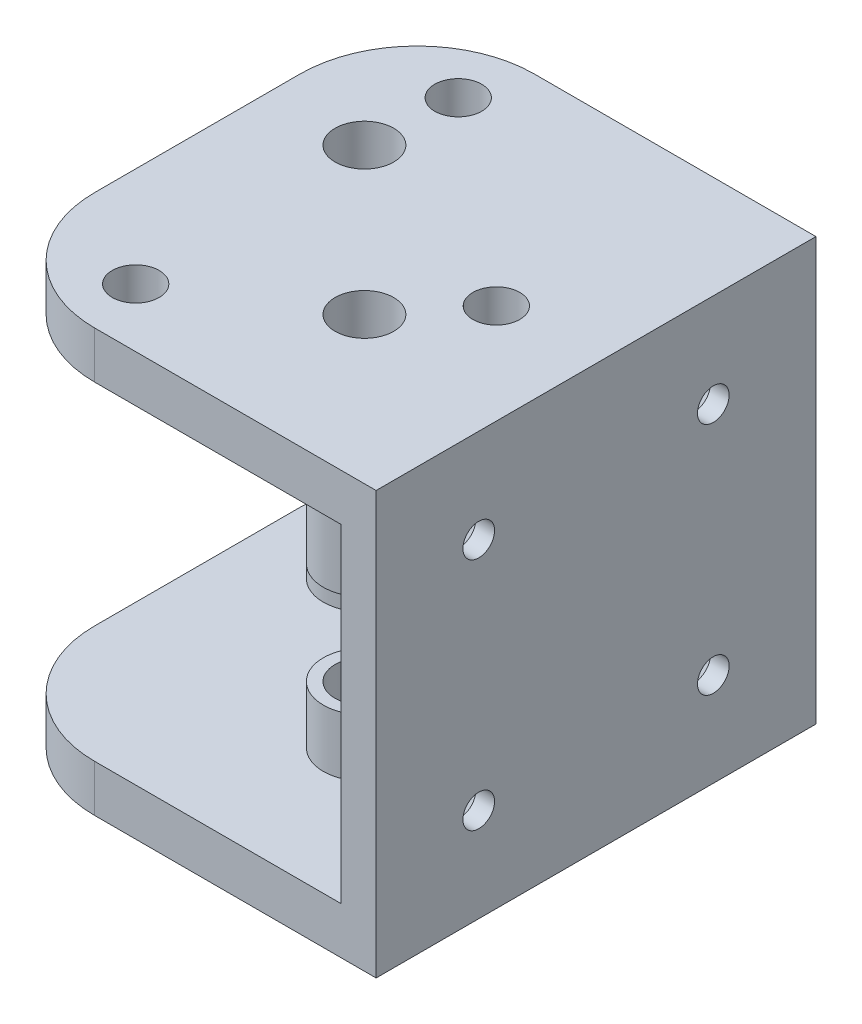
SolidWorks part; units mm, degrees
ref_plane "Front Plane" through (0, 0, 0) normal (0, 0, 1) x (1, 0, 0)
ref_plane "Top Plane" through (0, 0, 0) normal (0, 1, 0) x (1, 0, 0)
ref_plane "Right Plane" through (0, 0, 0) normal (1, 0, 0) x (0, 0, -1)
sketch "TopSketch1" plane through (0, 0, 0) normal (0, 1, 0) x (1, 0, 0)
  line L1 (0, 0) -> (34, 0)
  line L2 (0, 0) -> (0, 37.5)
  line L3 (0, 37.5) -> (34, 37.5)
  line L4 (34, 0) -> (34, 37.5)
  circle A0 centre (8.5, 32.5) radius 2
  circle A1 centre (8.5, 5) radius 2
  circle A2 centre (20.5, 12.5) radius 2.5
  circle A3 centre (8, 25) radius 2.5
  dimension "D7" = 4
  dimension "D8" = 5
  dimension "D2" = 12.5
  dimension "D3" = 12.5
  dimension "D4" = 5
  dimension "D5" = 5
  dimension "D10" = 37.5
  dimension "D9" = 12.5
  dimension "D12" = 13.5
  dimension "D6" = 25.5
  dimension "D11" = 8
  dimension "D13" = 12.5
extrude "Boss-Extrude1" add sketch "TopSketch1" along normal blind 4
sketch "TopLeftRiser" plane through (0, 0, 0) normal (0, -1, 0) x (1, 0, 0)
  line L0 (5.75, -27.681) -> (5.75, -37.5)
  line L1 (34, -37.5) -> (0, -37.5) construction
  line L2 (5.75, -37.5) -> (10.25, -37.5)
  line L3 (10.25, -37.5) -> (10.25, -27.681)
  arc A0 (10.25, -27.681) -> (5.75, -27.681) centre (8, -25) ccw
  circle A1 centre (8, -25) radius 2.5 construction
  circle A2 centre (8, -25) radius 2.5
  point P12 (8, -37.5)
  dimension "D1" = 7
  dimension "D2" = 4.5
extrude "TopLeftRiserBoss-Extrude2" add sketch "TopLeftRiser" along normal blind 4.9
sketch "TopRightRiser" plane through (0, 0, 0) normal (0, -1, 0) x (1, 0, 0)
  line L0 (18.25, -15.181) -> (18.25, -37.5)
  line L1 (34, -37.5) -> (10.25, -37.5) construction
  line L2 (18.25, -37.5) -> (22.75, -37.5)
  line L3 (22.75, -37.5) -> (22.75, -15.181)
  line L4 (5.75, -37.5) -> (10.25, -37.5) construction
  circle A0 centre (20.5, -12.5) radius 2.5
  circle A1 centre (20.5, -12.5) radius 2.5 construction
  arc A2 (22.75, -15.181) -> (18.25, -15.181) centre (20.5, -12.5) ccw
  arc A3 (10.25, -27.681) -> (5.75, -27.681) centre (8, -25) ccw construction
  point P15 (20.5, -37.5)
extrude "topRightRiserBoss-Extrude3" add sketch "TopRightRiser" along normal blind 14.4
sketch "MidWallSketch3" plane through (0, 0, 0) normal (0, -1, 0) x (1, 0, 0)
  line L1 (0, -34.5) -> (10.25, -34.5)
  line L2 (0, -34.5) -> (0, -37.5)
  line L3 (0, -37.5) -> (10.25, -37.5)
  line L4 (10.25, -34.5) -> (10.25, -37.5)
  line L5 (18.25, -34.5) -> (22.75, -34.5)
  line L6 (18.25, -34.5) -> (18.25, -37.5)
  line L7 (18.25, -37.5) -> (22.75, -37.5)
  line L8 (22.75, -34.5) -> (22.75, -37.5)
  line L9 (34, 0) -> (34, -37.5)
  line L10 (34, -37.5) -> (31, -37.5)
  line L11 (31, -37.5) -> (31, 0)
  line L14 (10.25, -37.5) -> (10.25, -27.681) construction
  line L15 (0, -37.5) -> (0, 0) construction
  line L16 (34, -37.5) -> (0, -37.5) construction
  line L17 (31, 0) -> (34, 0)
  line L19 (34, 0) -> (34, -37.5) construction
  line L20 (0, 0) -> (34, 0) construction
  line L21 (22.75, -37.5) -> (22.75, -15.181) construction
  line L22 (18.25, -15.181) -> (18.25, -37.5) construction
  dimension "D1" = 3
extrude "MidWallBoss-Extrude4" add sketch "MidWallSketch3" along normal blind 28
sketch "BottomSketch4" plane through (0, -28, 0) normal (0, -1, 0) x (1, 0, 0)
  line L0 (0, 0) -> (34, 0) construction
  line L1 (0, 0) -> (34, 0)
  line L2 (0, 0) -> (0, -37.5)
  line L3 (0, -37.5) -> (34, -37.5)
  line L4 (34, 0) -> (34, -37.5)
  line L5 (34, 0) -> (34, -37.5) construction
  line L6 (34, -37.5) -> (0, -37.5) construction
extrude "BottomBoss-Extrude5" add sketch "BottomSketch4" along normal blind 4
sketch "GBMountingHolesSketch7" plane through (34, 0, 0) normal (1, 0, 0) x (0, 0, -1)
  line L0 (37.5, 4) -> (37.5, -32) construction
  line L1 (0, 4) -> (37.5, 4) construction
  line L2 (37.5, -32) -> (0, -32) construction
  line L3 (0, 4) -> (0, -32) construction
  circle A0 centre (8.75, -4) radius 1
  circle A1 centre (8.75, -24) radius 1
  circle A2 centre (28.75, -24) radius 1
  circle A3 centre (28.75, -4) radius 1
  dimension "D7" = 2
  dimension "D1" = 20
  dimension "D2" = 8.75
  dimension "D3" = 8
  dimension "D4" = 20
  dimension "D5" = 8
  dimension "D6" = 8.75
extrude "GBMountingHolesCut-Extrude5" cut sketch "GBMountingHolesSketch7" against normal blind 3
sketch "LowerLeftRiser" plane through (0, -28, 0) normal (0, 1, 0) x (1, 0, 0)
  line L0 (5.75, 27.681) -> (5.75, 34.5)
  line L1 (5.75, 34.5) -> (10.25, 34.5)
  line L2 (10.25, 34.5) -> (10.25, 27.681)
  line L3 (5.75, 34.5) -> (10.25, 34.5) construction
  line L4 (5.75, 27.681) -> (5.75, 34.5) construction
  line L5 (10.25, 34.5) -> (10.25, 27.681) construction
  circle A0 centre (8, 25) radius 2.5
  arc A1 (5.75, 27.681) -> (10.25, 27.681) centre (8, 25) ccw
  circle A2 centre (8, 25) radius 2.5 construction
  arc A3 (5.75, 27.681) -> (10.25, 27.681) centre (8, 25) ccw construction
extrude "LowerLeftRiserBoss-Extrude6" add sketch "LowerLeftRiser" along normal blind 14.4
sketch "LowerRightRiser" plane through (0, -28, 0) normal (0, 1, 0) x (1, 0, 0)
  line L0 (18.25, 15.181) -> (18.25, 34.5)
  line L1 (18.25, 34.5) -> (22.75, 34.5)
  line L2 (22.75, 34.5) -> (22.75, 15.181)
  line L3 (18.25, 34.5) -> (22.75, 34.5) construction
  line L4 (18.25, 15.181) -> (18.25, 34.5) construction
  line L5 (22.75, 34.5) -> (22.75, 15.181) construction
  circle A0 centre (20.5, 12.5) radius 2.5
  circle A1 centre (20.5, 12.5) radius 2.5 construction
  arc A2 (18.25, 15.181) -> (22.75, 15.181) centre (20.5, 12.5) ccw
  arc A3 (18.25, 15.181) -> (22.75, 15.181) centre (20.5, 12.5) ccw construction
extrude "LowerRightRiserBoss-Extrude7" add sketch "LowerRightRiser" along normal blind 4.9
fillet "Fillet1" radius 10 3 edges at (0, -30, 0) (0, 2, 0) (0, -14, -37.5)
sketch "TopLeftInset" plane through (0, -4.9, 0) normal (0, -1, 0) x (1, 0, 0)
  line L0 (5.75, -27.681) -> (5.75, -34.5)
  line L1 (5.75, -34.5) -> (10.25, -34.5)
  line L2 (10.25, -34.5) -> (10.25, -27.681)
  line L3 (10.25, -34.5) -> (5.75, -34.5) construction
  line L4 (5.75, -34.5) -> (5.75, -27.681) construction
  line L5 (10.25, -27.681) -> (10.25, -34.5) construction
  arc A0 (5.75, -27.681) -> (10.25, -27.681) centre (8, -25) ccw
  arc A1 (10.25, -27.681) -> (5.75, -27.681) centre (8, -25) ccw construction
extrude "TopLeftInsetCut-Extrude1" cut sketch "TopLeftInset" against normal blind 1
sketch "TopRightInset" plane through (0, -14.4, 0) normal (0, -1, 0) x (1, 0, 0)
  line L0 (18.25, -15.181) -> (18.25, -34.5)
  line L1 (18.25, -34.5) -> (22.75, -34.5)
  line L2 (22.75, -34.5) -> (22.75, -15.181)
  line L3 (22.75, -34.5) -> (18.25, -34.5) construction
  line L4 (18.25, -34.5) -> (18.25, -15.181) construction
  line L5 (22.75, -15.181) -> (22.75, -34.5) construction
  arc A0 (18.25, -15.181) -> (22.75, -15.181) centre (20.5, -12.5) ccw
  arc A1 (22.75, -15.181) -> (18.25, -15.181) centre (20.5, -12.5) ccw construction
extrude "TopRightInsetCut-Extrude2" cut sketch "TopRightInset" against normal blind 1
sketch "LowerLeftInset" plane through (0, -13.6, 0) normal (0, 1, 0) x (1, 0, 0)
  line L0 (5.75, 27.681) -> (5.75, 34.5)
  line L1 (5.75, 34.5) -> (10.25, 34.5)
  line L2 (10.25, 34.5) -> (10.25, 27.681)
  line L3 (5.75, 34.5) -> (10.25, 34.5) construction
  line L4 (5.75, 27.681) -> (5.75, 34.5) construction
  line L5 (10.25, 34.5) -> (10.25, 27.681) construction
  arc A0 (10.25, 27.681) -> (5.75, 27.681) centre (8, 25) ccw
  arc A1 (5.75, 27.681) -> (10.25, 27.681) centre (8, 25) ccw construction
extrude "LowerLeftInsetCut-Extrude3" cut sketch "LowerLeftInset" against normal blind 1
sketch "LowerRightInset" plane through (0, -23.1, 0) normal (0, 1, 0) x (1, 0, 0)
  line L0 (18.25, 15.181) -> (18.25, 34.5)
  line L1 (18.25, 34.5) -> (22.75, 34.5)
  line L2 (22.75, 34.5) -> (22.75, 15.181)
  line L3 (18.25, 34.5) -> (22.75, 34.5) construction
  line L4 (18.25, 15.181) -> (18.25, 34.5) construction
  line L5 (22.75, 34.5) -> (22.75, 15.181) construction
  arc A2 (22.75, 15.181) -> (18.25, 15.181) centre (20.5, 12.5) ccw
  arc A3 (18.25, 15.181) -> (22.75, 15.181) centre (20.5, 12.5) ccw construction
extrude "LowerRightInsetCut-Extrude4" cut sketch "LowerRightInset" against normal blind 1
sketch "PushPinHoleSketch1" plane through (0, -32, 0) normal (0, -1, 0) x (1, 0, 0)
  circle A0 centre (20.5, -12.5) radius 1
  circle A1 centre (8, -25) radius 1
  circle A2 centre (8, -25) radius 2.5 construction
  circle A3 centre (20.5, -12.5) radius 2.5 construction
  dimension "D1" = 2
extrude "PushPinHoleCut-Extrude1" cut sketch "PushPinHoleSketch1" against normal through all
sketch "BottomLeftMountHoleAccessSketch1" plane through (5.75, 0, 0) normal (-1, 0, 0) x (0, 0, 1)
  circle A0 centre (-28.75, -24) radius 2.75
  dimension "D1" = 5.5
extrude "BottomLeftMountHoleAccessCut-Extrude2" cut sketch "BottomLeftMountHoleAccessSketch1" against normal blind 15 and the other way blind 10
sketch "Sketch11" plane through (31, 0, 0) normal (-1, 0, 0) x (0, 0, 1)
  point P0 (-8.75, -24)
  point P3 (-28.75, -24)
  point P6 (-8.75, -4)
  point P9 (-28.75, -4)
hole_wizard "CSK for M2.5 Flat Head Machine Screw1" positions "Sketch11" profile "Sketch12" countersink size "M2.5" standard "ANSI Metric" end condition through all
sketch "Sketch12" plane through (31, -24, -8.75) normal (0, 1, 0) x (0, 0, 1)
  line L0 (0, 0) -> (0, 3)
  line L1 (0, 3) -> (1.35, 3)
  line L2 (1.35, 3) -> (1.35, 1.4)
  line L3 (1.35, 1.4) -> (2.75, 0)
  line L5 (2.75, 0) -> (0, 0)
  line L6 (-1.35, 1.4) -> (-2.75, 0) construction
  line L11 (0, -6.35) -> (0, 107.95) construction
  dimension "Thru Hole Dia." = 2.7
  dimension "Thru Hole Depth" = 3
  dimension "Near C'Sink Dia." = 5.5
  dimension "Near C'Sink Angle" = 90
sketch "TopLeftMountHoleAccessSketch13" plane through (18.25, 0, 0) normal (-1, 0, 0) x (0, 0, 1)
  circle A0 centre (-28.75, -4) radius 2.75
  dimension "D1" = 5.5
extrude "TopLeftMountHoleAccessCut-Extrude1" cut sketch "TopLeftMountHoleAccessSketch13" against normal up to next
sketch "TopLeftElipseMountHoleAccessSketch14" plane through (5.75, 0, 0) normal (-1, 0, 0) x (0, 0, 1)
  arc A0 (-28.75, -1.25) -> (-28.75, -6.75) centre (-28.75, -4) ccw
  circle A1 centre (-28.75, -4) radius 2.75 construction
  ellipse E0 centre (-28.75, -4) end of major axis (-28.75, -1.25) minor radius 1.069 (-28.75, -6.75) -> (-28.75, -1.25) ccw
extrude "TopLeftElipseMountHoleAccessCut-Extrude2" cut sketch "TopLeftElipseMountHoleAccessSketch14" against normal blind 10
sketch "TopBackClampHoleSketch13" plane through (0, 4, 0) normal (0, 1, 0) x (1, 0, 0)
  line L0 (34, 37.5) -> (10, 37.5) construction
  line L1 (34, 0) -> (34, 37.5) construction
  circle A0 centre (25.5, 18.75) radius 2
  arc A1 (8.5, 34.5) -> (10.25, 31.5318) centre (8.5, 32.5) ccw construction
  dimension "D1" = 18.75
  dimension "D2" = 8.5
extrude "TopBackClampHoleCut-Extrude1" cut sketch "TopBackClampHoleSketch13" against normal blind 4
equation "\"GABDepth\"= \"GABDistanceFromBackToFirstPulley\" + \"GABPulleyDDistanceBetween\" + \"GABDistanceFromPulleyToFront\""
equation "\"GABWidth\"= \"StandardWallThickness\" + \"GABDistanceFromLSideToPulley\" + \"GABPulleyWDistanceBetween\" + \"GABDistanceFromPulleyToRSide\""
equation "\"GABLowerHeight\"= 4mm"
equation "\"GABUpperHeight\"= 4mm"
equation "\"GABMidWallHeight\"= 28mm'Must equal 28 or changes alignment"
equation "\"StandardWallThickness\"= 3mm"
equation "\"GABMidShortRiserHeight\"= \"GABMidWallHeight\" / 2 - \"20TGT2PulleyWidth\"'Equals 5.3"
equation "\"LinearGBMountHolesXDistance\"= 20mm'Spec"
equation "\"GABHeight\"= \"GABLowerHeight\" + \"GABMidWallHeight\" + \"GABUpperHeight\""
equation "\"GBMountingHoleDiameter\"= 2mm"
equation "\"GABMidLongRiserHeight\"= \"GABMidWallHeight\" - \"GABMidShortRiserHeight\" - \"20TGT2PulleyWidth\"'Equals 14"
equation "\"GABLRClampHoleOffsetFromSide\"= 5mm"
equation "\"GABDistanceFromBackToFirstPulley\"= 13.5mm"
equation "\"GABPulleyDDistanceBetween\"= 12.5mm'From the100"
equation "\"GABPulleyWDistanceBetween\"= 14.5mm'From the100"
equation "\"GABDistanceFromPulleyToFront\"= 8mm"
equation "\"GABDistanceFromLSideToPulley\"= 9.5mm + \"StandardWallThickness\""
equation "\"GABDistanceFromPulleyToRSide\"= 7.5mm"
equation "\"GABDistanceToFrontRearClampHoles\"= 8.5mm"
equation "\"SteelShaft5mmHoleDiameter\"= 5mm"
equation "\"20TGT2PulleyWidth\"= 8.7mm'The STL of the Pulley in the diagram is a bit larger"
equation "\"7mmx1mmSpacerDiameter\"= 7mm"
equation "\"7mmx1mmSpacerHeight\"= 1mm"
equation "\"GABRiserBossOffset\"= 0.4mm'Aligns Pulleys inside edges to be 2.5mm (.5mm apart top to bottom)"
equation "\"D2@TopSketch1\" = \"GABPulleyDDistanceBetween\""
equation "\"D3@TopSketch1\" = \"GABPulleyDDistanceBetween\""
equation "\"D4@TopSketch1\" = \"GABLRClampHoleOffsetFromSide\""
equation "\"D5@TopSketch1\" = \"GABLRClampHoleOffsetFromSide\""
equation "\"D8@TopSketch1\" = \"SteelShaft5mmHoleDiameter\""
equation "\"D10@TopSketch1\" = \"GABWidth\""
equation "\"D9@TopSketch1\" = \"GABDistanceFromLSideToPulley\""
equation "\"D12@TopSketch1\"=\"GABDistanceFromBackToFirstPulley\""
equation "\"D1@Boss-Extrude1\"=\"GABUpperHeight\""
equation "\"D1@TopLeftRiser\" = \"7mmx1mmSpacerDiameter\""
equation "\"D1@TopLeftRiserBoss-Extrude2\" = \"GABMidShortRiserHeight\" - \"GABRiserBossOffset\""
equation "\"D1@topRightRiserBoss-Extrude3\" = \"GABMidLongRiserHeight\" + \"GABRiserBossOffset\""
equation "\"D1@MidWallBoss-Extrude4\" = \"GABMidWallHeight\""
equation "\"D1@BottomBoss-Extrude5\" = \"GABLowerHeight\""
equation "\"D1@LowerLeftRiserBoss-Extrude6\" = \"GABMidLongRiserHeight\" + \"GABRiserBossOffset\""
equation "\"D1@LowerRightRiserBoss-Extrude7\" = \"GABMidShortRiserHeight\" - \"GABRiserBossOffset\""
equation "\"D1@GBMountingHolesSketch7\" = \"LinearGBMountHolesXDistance\""
equation "\"D2@GBMountingHolesSketch7\" =  ( \"GABWidth\" - \"LinearGBMountHolesXDistance\" )  / 2"
equation "\"D3@GBMountingHolesSketch7\" =  ( \"GABHeight\" - \"LinearGBMountHolesXDistance\" )  / 2"
equation "\"D4@GBMountingHolesSketch7\"=\"LinearGBMountHolesYDistance\""
equation "\"D7@GBMountingHolesSketch7\"=\"GBMountingHoleDiameter\""
equation "\"D1@TopLeftInsetCut-Extrude1\" = \"7mmx1mmSpacerHeight\""
equation "\"D1@TopRightInsetCut-Extrude2\" = \"7mmx1mmSpacerHeight\""
equation "\"D1@LowerLeftInsetCut-Extrude3\" = \"7mmx1mmSpacerHeight\""
equation "\"D1@LowerRightInsetCut-Extrude4\" = \"7mmx1mmSpacerHeight\""
equation "\"D1@GBMountingHolesCut-Extrude5\" = \"StandardWallThickness\""
equation "\"D6@TopSketch1\"=\"GABDepth\" - \"GABDistanceToFrontRearClampHoles\""
equation "\"D11@TopSketch1\"=\"GABDistanceFromPulleyToFront\""
equation "\"LinearGBMountHolesYDistance\"= 20mm'Spec"
equation "\"StealPinPushHoleDiameter\"= 2mm"
equation "\"D1@PushPinHoleSketch1\" = \"StealPinPushHoleDiameter\""
equation "\"M3HeatInsertHoleDiameter\"= 4mm'Spec"
equation "\"D7@TopSketch1\"=\"M3HeatInsertHoleDiameter\""
equation "\"D1@TopBackClampHoleSketch13\" = \"GABWidth\" / 2"
equation "\"D2@TopBackClampHoleSketch13\" = \"GABDistanceToFrontRearClampHoles\""
equation "\"D1@TopBackClampHoleCut-Extrude1\" = \"GABUpperHeight\""
